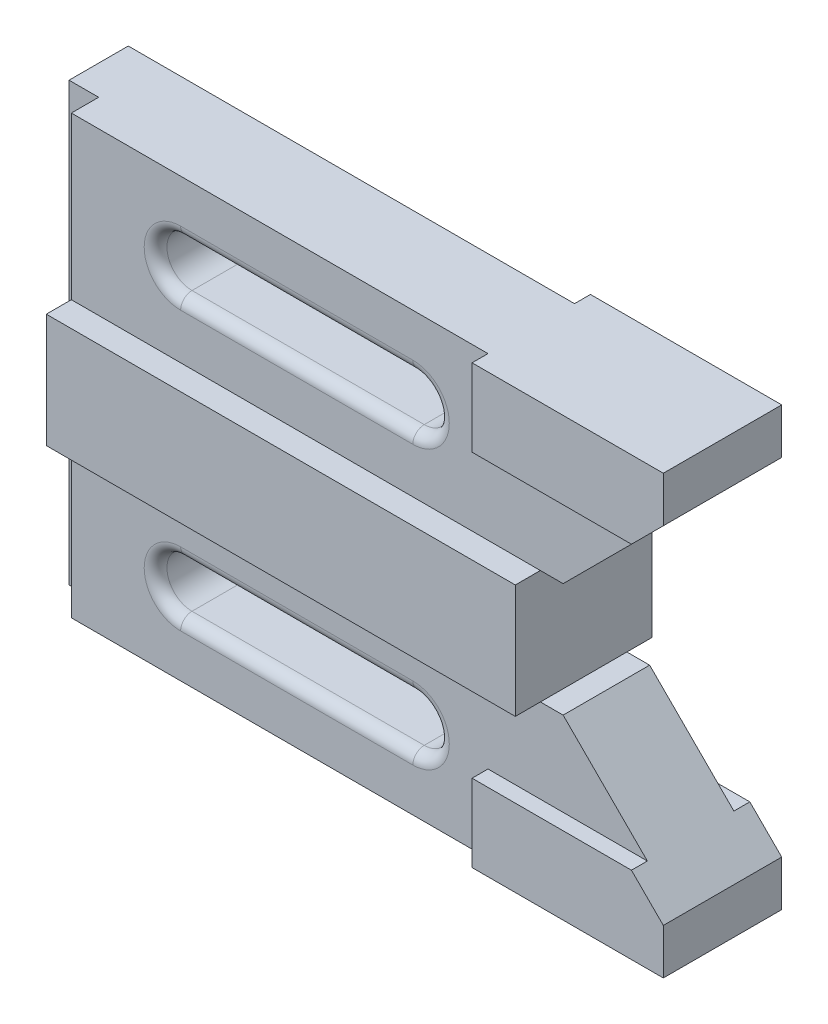
SolidWorks part; units mm, degrees
material "1060 Alloy"
ref_plane "Front Plane" through (0, 0, 0) normal (0, 0, 1) x (1, 0, 0)
ref_plane "Top Plane" through (0, 0, 0) normal (0, 1, 0) x (1, 0, 0)
ref_plane "Right Plane" through (0, 0, 0) normal (1, 0, 0) x (0, 0, -1)
sketch "Sketch1" plane through (0, 0, 0) normal (0, 0, 1) x (1, 0, 0)
  line L0 (0, 0) -> (0, 48)
  line L1 (0, 48) -> (140, 48)
  line L2 (0, 0) -> (109.5, 0)
  line L3 (109.5, 0) -> (109.5, 12.5)
  line L4 (109.5, 12.5) -> (114.5, 12.5)
  line L5 (114.5, 12.5) -> (140, 38)
  line L6 (140, 38) -> (140, 48)
  line L7 (109.5, 12.5) -> (0, 12.5)
  line L8 (98, 48) -> (98, 31)
  line L9 (98, 31) -> (133, 31)
  line L10 (0, 30.5) -> (30.5, 30.5)
  line L11 (30.5, 30.5) -> (81.5, 30.5) construction
  line L12 (30.5, 36) -> (81.5, 36)
  line L13 (30.5, 25) -> (81.5, 25)
  arc A0 (30.5, 36) -> (30.5, 25) centre (30.5, 30.5) ccw
  arc A1 (81.5, 25) -> (81.5, 36) centre (81.5, 30.5) ccw
  point P14 (56, 30.5)
  dimension "D13" = 5.5
  dimension "D1" = 48
  dimension "D2" = 140
  dimension "D3" = 10
  dimension "D4" = 45
  dimension "D5" = 35.5
  dimension "D6" = 12.5
  dimension "D7" = 30.5
  dimension "D8" = 17
  dimension "D9" = 35
  dimension "D10" = 17.5
  dimension "D11" = 30.5
  dimension "D12" = 51
extrude "Boss-Extrude2" add sketch "Sketch1" along normal mid plane 30 contours L3 L7 L0 L2 region at (54.75, 6.25, 0)
extrude "Boss-Extrude3" add sketch "Sketch1<4>" along normal mid plane 19 contours A1 L13 A0 L0 L7 L4 L5 L9 L8 L1 L12 region at (1.3766, 21.5, 0)
sketch "Sketch1<4>" plane through (0, 0, 0) normal (0, 0, 1) x (1, 0, 0) same geometry as "Sketch1"
extrude "Boss-Extrude4" add sketch "Sketch1<5>" along normal mid plane 26 contours L8 L9 L5 L6 L1 region at (118.3367, 39.7191, 0)
sketch "Sketch1<5>" plane through (0, 0, 0) normal (0, 0, 1) x (1, 0, 0) same geometry as "Sketch1"
mirror "Mirror1" about plane through (0, 0, 15) normal (0, 1, 0) of bodies 104
sketch "Sketch3" plane through (0, 48, 0) normal (0, 1, 0) x (1, 0, 0)
  line L1 (0, -15) -> (6.5, -15)
  line L2 (0, -15) -> (0, -3.5)
  line L3 (0, -3.5) -> (6.5, -3.5)
  line L4 (6.5, -15) -> (6.5, -3.5)
  dimension "D1" = 6.5
  dimension "D2" = 11.5
extrude "Cut-Extrude1" cut sketch "Sketch3" against normal blind 96
fillet "Fillet1" radius 2.5 16 edges at (56, -25, 9.5) (87, -30.5, 9.5) (25, -30.5, 9.5) (56, -36, 9.5) (25, -30.5, -9.5) (56, -25, -9.5) (87, -30.5, -9.5) (56, -36, -9.5) (25, 30.5, -9.5) (56, 36, -9.5) (56, 25, -9.5) (87, 30.5, -9.5) (87, 30.5, 9.5) (56, 36, 9.5) (25, 30.5, 9.5) (56, 25, 9.5)
